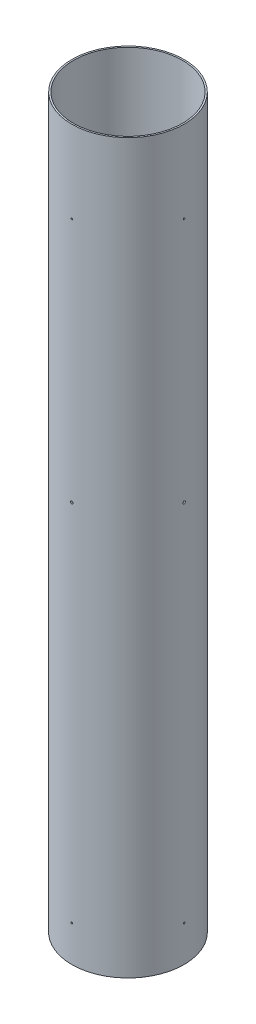
SolidWorks part; units mm, degrees
material "A-Glass Fiber"
ref_plane "Front Plane" through (0, 0, 0) normal (0, 0, 1) x (1, 0, 0)
ref_plane "Top Plane" through (0, 0, 0) normal (0, 1, 0) x (1, 0, 0)
ref_plane "Right Plane" through (0, 0, 0) normal (1, 0, 0) x (0, 0, -1)
sketch "Sketch1" plane through (0, 0, 0) normal (0, 1, 0) x (1, 0, 0)
  circle A0 centre (0, 0) radius 76.1746
  circle A1 centre (0, 0) radius 78.359
  dimension "D1" = 156.718
  dimension "D2" = 152.3492
extrude "Boss-Extrude1" add sketch "Sketch1" along normal blind 1016
ref_axis "Axis1" through (0, 1016, 0) along (0, -1, 0)
sketch "Sketch3" plane through (0, 0, 0) normal (0, 0, 1) x (1, 0, 0)
  line L0 (0, 558.8) -> (0, 1016) construction
  line L1 (78.359, 1016) -> (-78.359, 1016) construction
  line L2 (0, 0) -> (0, 50.1849) construction
  circle A0 centre (0, 558.8) radius 1.75
  circle A1 centre (0, 50.1849) radius 1.0922
  circle A2 centre (0, 901.7) radius 1.0922
  dimension "D2" = 3.5
  dimension "D3" = 2.1844
  dimension "D4" = 2.1844
  dimension "D1" = 457.2
  dimension "D5" = 114.3
extrude "Cut-Extrude1" cut sketch "Sketch3" against normal through all
pattern_circular "CirPattern1" count 4 over 360 about axis through (0, 1016, 0) along (0, -1, 0) of "Cut-Extrude1"
equation "\"Fwd_Tube_Length\" = 40in"
equation "\"D1@Boss-Extrude1\" = \"Fwd_Tube_Length\""
equation "\"BKHD_Screw_Diam\"= 3.5mm"
equation "\"Fwd_BKHD_From_Top\" = 18in"
equation "\"D2@Sketch3\"=\"BKHD_Screw_Diam\""
equation "\"D1@Sketch3\"=\"Fwd_BKHD_From_Top\""
equation "\"Bodytube_OD\" = 6.17in"
equation "\"Bodytube_ID\" = 5.998in"
equation "\"D2@Sketch1\"=\"Bodytube_ID\""
equation "\"D1@Sketch1\"=\"Bodytube_OD\""
equation "\"Shear_Screw_Diameter\" = 0.086in"
equation "\"D3@Sketch3\"=\"Shear_Screw_Diameter\""
equation "\"D4@Sketch3\"=\"Shear_Screw_Diameter\""
equation "\"Shear_Screw_Coupler_Location\" = 4.5in"
equation "\"D5@Sketch3\"=\"Shear_Screw_Coupler_Location\""
